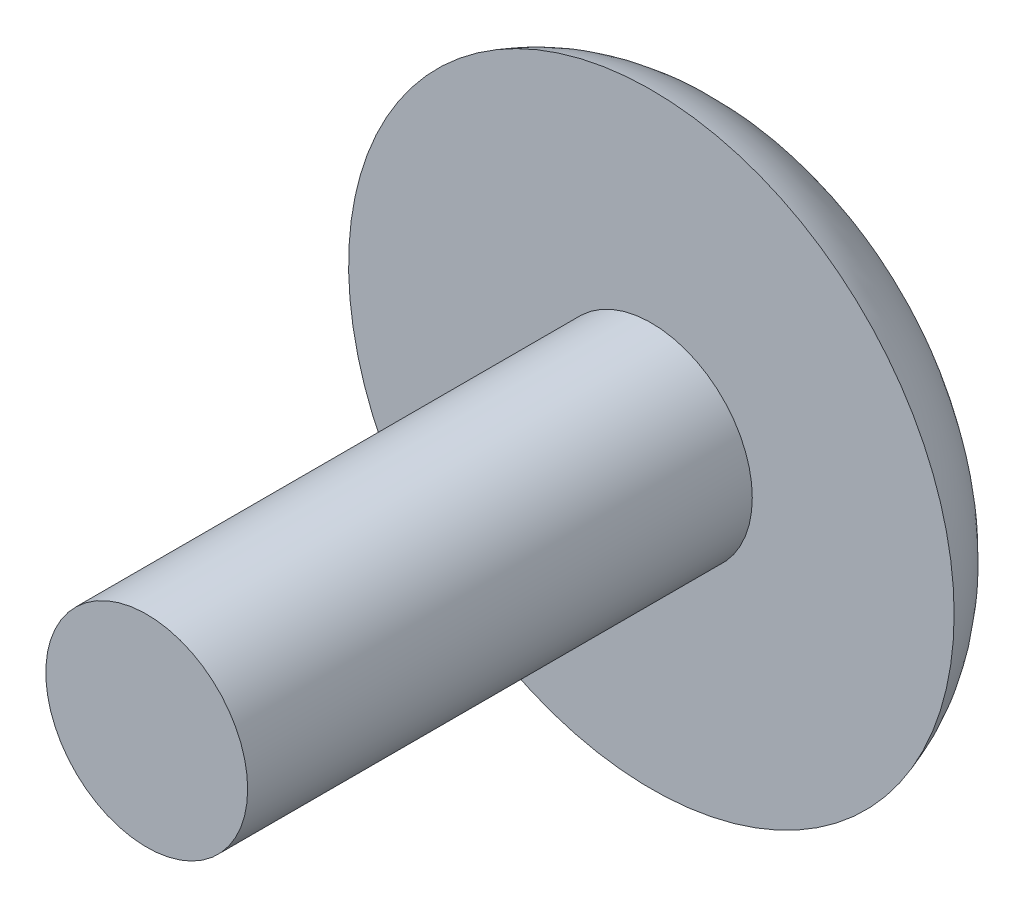
SolidWorks part; units mm, degrees
ref_plane "前基準面" through (0, 0, 0) normal (0, 0, 1) x (1, 0, 0)
ref_plane "上基準面" through (0, 0, 0) normal (0, 1, 0) x (1, 0, 0)
ref_plane "右基準面" through (0, 0, 0) normal (1, 0, 0) x (0, 0, -1)
sketch "草圖1" plane through (0, 0, 0) normal (0, 0, 1) x (1, 0, 0)
  circle A0 centre (0, 0) radius 1.5
  dimension "D1" = 3
extrude "伸長1" add sketch "草圖1" along normal blind 0.5
sketch "草圖2" plane through (0, 0, 0.5) normal (0, 0, 1) x (1, 0, 0)
  circle A0 centre (0, 0) radius 0.5
  dimension "D1" = 1
extrude "伸長2" add sketch "草圖2" along normal blind 2.5
sketch "草圖3" plane through (0, 0, 0) normal (0, 0, -1) x (-1, 0, 0)
  line L1 (-0.115, 1.2) -> (0.115, 1.2)
  line L2 (-0.115, 1.2) -> (-0.115, -1.2)
  line L3 (-0.115, -1.2) -> (0.115, -1.2)
  line L4 (0.115, 1.2) -> (0.115, -1.2)
  line L5 (-0.115, 1.2) -> (0.115, -1.2) construction
  line L6 (-0.115, -1.2) -> (0.115, 1.2) construction
  point P0 (0, 0)
  dimension "D1" = 2.4
  dimension "D2" = 0.23
sketch "草圖4" plane through (0, 0, 0) normal (1, 0, 0) x (0, 0, -1)
  line L0 (0, 0) -> (-0.85, 0) construction
  point P0 (-0.85, 0)
  dimension "D1" = 0.85
loft "除料-疊層拉伸1" cut profiles "草圖3", "草圖4"
pattern_circular "環狀複製排列1" count 4 over 360 about axis through (0, 0, 3) along (0, 0, -1) of "除料-疊層拉伸1"
fillet "圓角2" radius 0.7 1 edges at (1.5, 0, 0)
sketch "草圖5" plane through (0, 0, 3) normal (0, 0, 1) x (1, 0, 0)
  circle A0 centre (0, 0) radius 0.5 construction
  circle A1 centre (0, 0) radius 0.5
